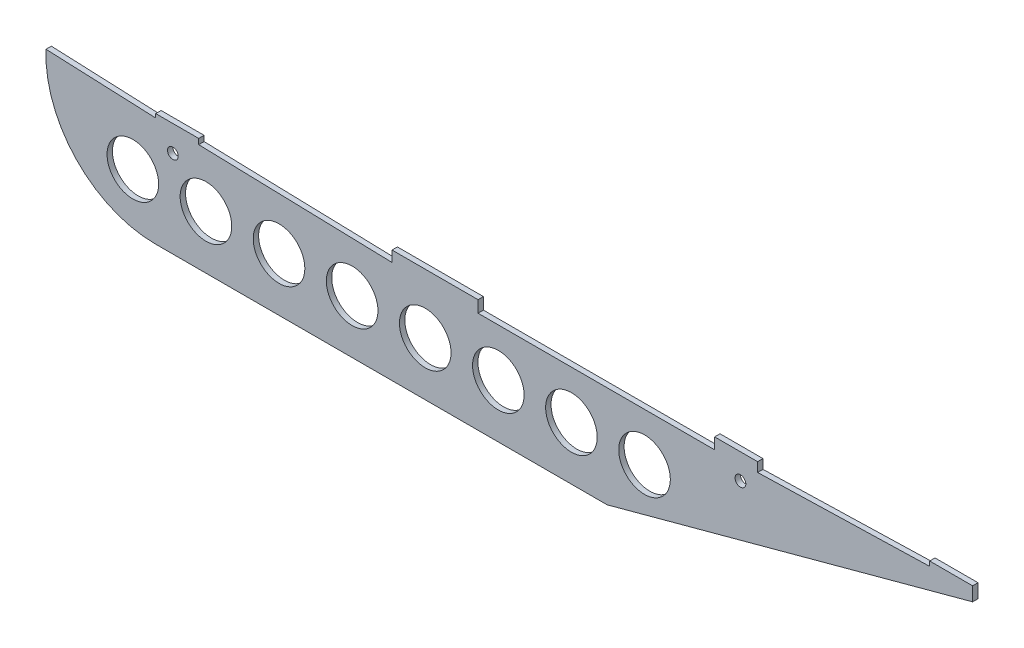
SolidWorks part; units mm, degrees
material "Birch Ply"
ref_plane "Front Plane" through (0, 0, 0) normal (0, 0, 1) x (1, 0, 0)
ref_plane "Top Plane" through (0, 0, 0) normal (0, 1, 0) x (1, 0, 0)
ref_plane "Right Plane" through (0, 0, 0) normal (1, 0, 0) x (0, 0, -1)
sketch "Sketch1" plane through (0, 0, 0) normal (0, 0, 1) x (1, 0, 0)
  line L1 (331.4792, -67.3278) -> (547.3792, -9.0155)
  line L2 (0, 0) -> (-2.5762, -60.2421) construction
  line L3 (547.3792, -0.8036) -> (547.3792, -9.0155)
  line L4 (547.3792, -0.8036) -> (521.9792, -0.8036)
  line L5 (521.9792, -0.8036) -> (521.9792, -3.5503)
  line L6 (521.9792, -3.5503) -> (420.3792, -6.318)
  line L7 (420.3792, -6.318) -> (420.3792, -0.8036)
  line L8 (420.3792, -0.8036) -> (394.9792, -0.8036)
  line L9 (394.9792, -0.8036) -> (394.9792, -7.4329)
  line L10 (394.9792, -7.4329) -> (255.2141, -7.4329)
  line L11 (255.2141, -7.4329) -> (255.2141, -0.5036)
  line L12 (255.2141, -0.5036) -> (204.4141, -0.5036)
  line L13 (204.4141, -0.5036) -> (204.4141, -6.8758)
  line L14 (331.4792, -67.3278) -> (64.5102, -67.3278)
  line L15 (204.4141, -6.8758) -> (90.2232, -3.7073)
  line L16 (90.2232, -3.7073) -> (90.2232, -0.5036)
  line L18 (90.2232, -0.5036) -> (64.8232, -0.5036)
  line L19 (64.8232, -0.5036) -> (64.8232, -2.7721)
  line L20 (64.8232, -2.7721) -> (0, 0)
  arc A0 (0, 0) -> (64.5102, -67.3278) centre (64.5102, -2.7587) ccw
  dimension "D19" = 2.7587
  dimension "D2" = 25.4
  dimension "D3" = 25.4
  dimension "D4" = 50.8
  dimension "D5" = 139.7652
  dimension "D6" = 114.2348
  dimension "D7" = 101.6
  dimension "D8" = 25.4
  dimension "D9" = 3.2036
  dimension "D10" = 6.3722
  dimension "D11" = 6.9293
  dimension "D12" = 6.6293
  dimension "D13" = 5.5145
  dimension "D14" = 2.7467
  dimension "D15" = 215.9
  dimension "D16" = 64.8232
  dimension "D17" = 66.8242
  dimension "D18" = 2.2684
  dimension "D22" = 58.3123
extrude "Boss-Extrude1" add sketch "Sketch1" along normal blind 1.5875 and the other way blind 1.5875 contours L15 L16 L18 L19 L20 A0 L14 L1 L3 L4 L5 L6 L7 L8 L9 L10 L11 L12 L13
sketch "Sketch2" plane through (0, 0, 0) normal (0, 0, 1) x (1, 0, 0)
  line L0 (420.3792, -0.8036) -> (394.9792, -0.8036) construction
  line L4 (547.3792, -0.8036) -> (547.3792, -9.0155) construction
  line L5 (90.2232, -0.5036) -> (64.8232, -0.5036) construction
  circle A0 centre (410.2192, -15.7436) radius 3.175
  circle A5 centre (74.9392, -15.7436) radius 3.175
  dimension "D1" = 6.35
  dimension "D4" = 472.44
  dimension "D10" = 6.35
  dimension "D2" = 14.94
  dimension "D5" = 15.24
  dimension "D3" = 137.16
extrude "Cut-Extrude1" cut sketch "Sketch2" along normal through all and the other way through all contours A0 | A5
sketch "Sketch3" plane through (0, 0, 0) normal (0, 0, 1) x (1, 0, 0)
  line L0 (353.5628, -35.7109) -> (51.3028, -35.7109) construction
  line L3 (360.0202, -59.6192) -> (357.5366, -50.4237) construction
  line L4 (331.4792, -67.3278) -> (547.3792, -9.0155) construction
  line L5 (83.8227, -24.8197) -> (77.1601, -18.0126) construction
  circle A0 centre (51.3028, -35.7109) radius 15.24
  circle A2 centre (94.4828, -35.7109) radius 15.24
  circle A3 centre (137.6628, -35.7109) radius 15.24
  circle A4 centre (180.8428, -35.7109) radius 15.24
  circle A5 centre (224.0228, -35.7109) radius 15.24
  circle A6 centre (267.2028, -35.7109) radius 15.24
  circle A7 centre (310.3828, -35.7109) radius 15.24
  circle A8 centre (353.5628, -35.7109) radius 15.24
  circle A10 centre (74.9392, -15.7436) radius 3.175 construction
  dimension "D2" = 30.48
  dimension "D1" = 30.48
  dimension "D3" = 30.48
  dimension "D4" = 30.48
  dimension "D5" = 30.48
  dimension "D6" = 30.48
  dimension "D7" = 30.48
  dimension "D8" = 43.18
  dimension "D9" = 30.48
  dimension "D11" = 9.525
  dimension "D20" = 43.18
  dimension "D21" = 43.18
  dimension "D22" = 43.18
  dimension "D23" = 43.18
  dimension "D24" = 43.18
  dimension "D25" = 43.18
  dimension "D10" = 9.525
extrude "Cut-Extrude2" cut sketch "Sketch3" against normal blind 2.54 and the other way blind 2.54 contours L0 A2 | A2 L0 | L0 A8 | A0 | A3 | A4 | A5 | A6 | A7 | A8 region at (94.4828, -35.7109, 0) region at (353.5628, -35.7109, 0)
